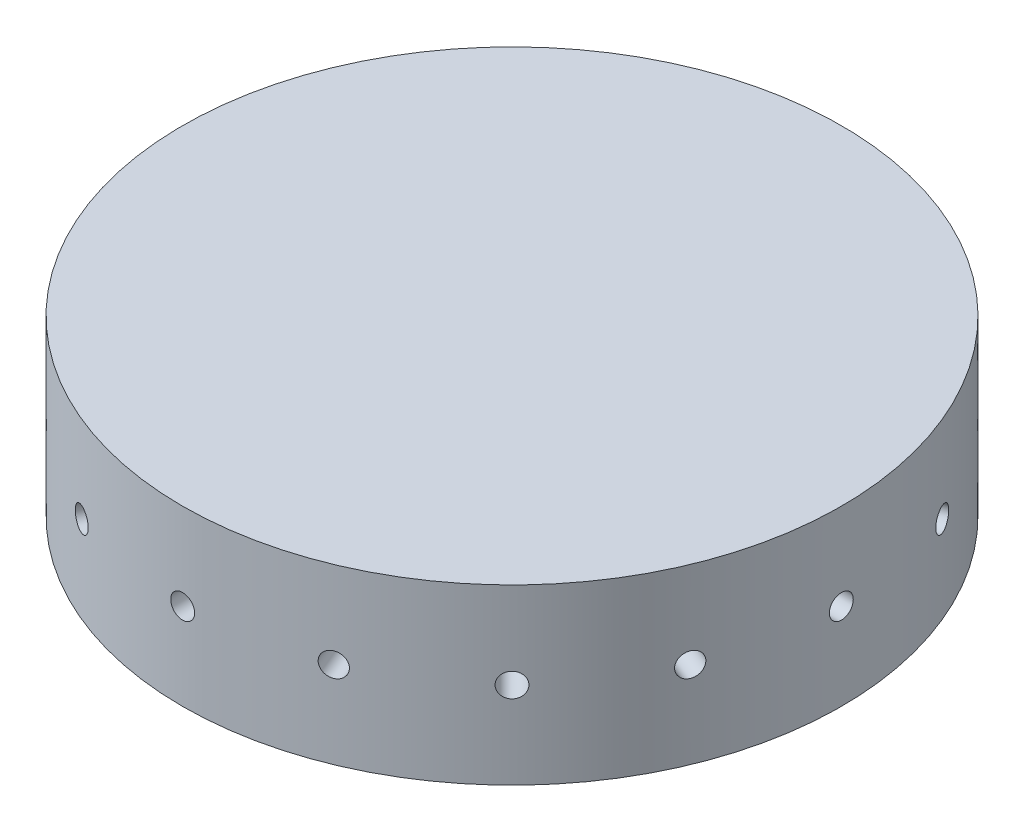
SolidWorks part; units mm, degrees
material "6061 Alloy"
ref_plane "Front Plane" through (0, 0, 0) normal (0, 0, 1) x (1, 0, 0)
ref_plane "Top Plane" through (0, 0, 0) normal (0, 1, 0) x (1, 0, 0)
ref_plane "Right Plane" through (0, 0, 0) normal (1, 0, 0) x (0, 0, -1)
sketch "Sketch1" plane through (0, 0, 0) normal (0, 1, 0) x (1, 0, 0)
  circle A0 centre (0, 0) radius 48.26
  dimension "D1" = 96.52
extrude "Boss-Extrude1" add sketch "Sketch1" along normal blind 25.4
ref_plane "Plane1" through (0, 0, 48.26) normal (0, 0, 1) x (1, 0, 0)
sketch "Sketch2" plane through (0, 0, 48.26) normal (0, 0, 1) x (1, 0, 0)
  line L0 (0, 25.4) -> (0, 0) construction
  line L1 (48.26, 25.4) -> (-48.26, 25.4) construction
  circle A0 centre (0, 12.7) radius 1.7526
  dimension "D1" = 3.5052
extrude "Screw Hole" cut sketch "Sketch2" against normal blind 12.7
pattern_circular "Hole Pattern" count 16 over 360 about axis through (0, 25.4, 0) along (0, -1, 0) of "Screw Hole" reverse direction yes
